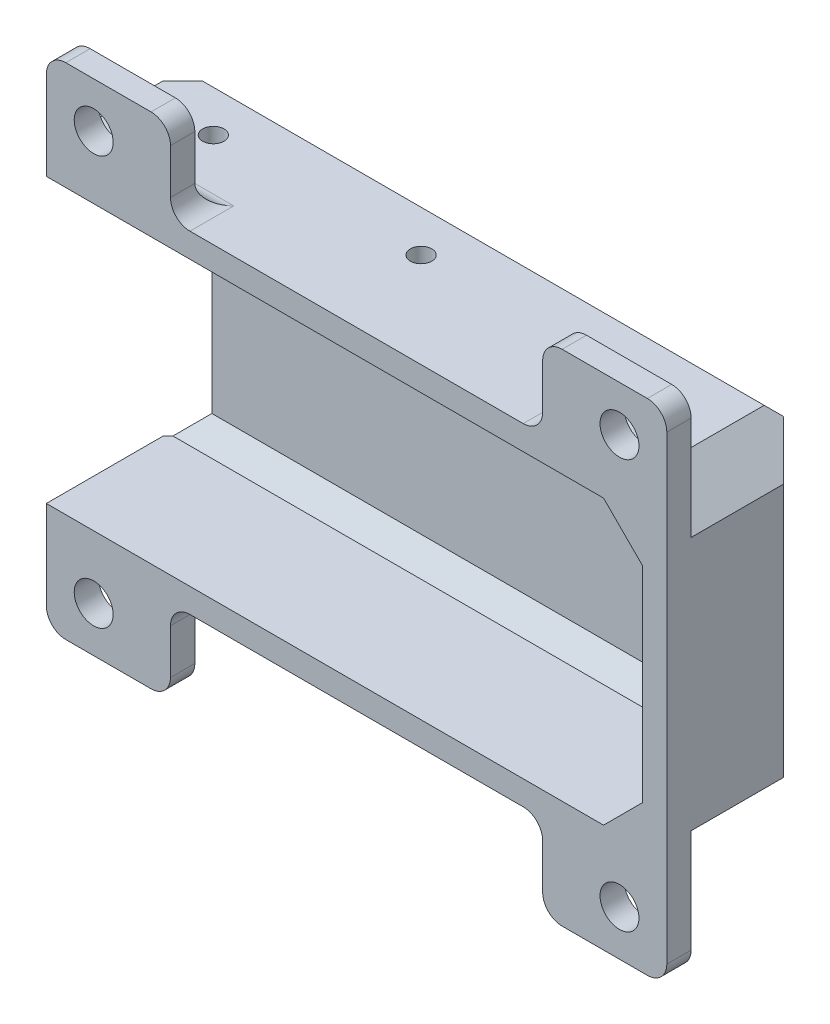
SolidWorks part; units mm, degrees
ref_plane "前视基准面" through (0, 0, 0) normal (0, 0, 1) x (1, 0, 0)
ref_plane "上视基准面" through (0, 0, 0) normal (0, 1, 0) x (1, 0, 0)
ref_plane "右视基准面" through (0, 0, 0) normal (1, 0, 0) x (0, 0, -1)
sketch "草图1" plane through (0, 0, 0) normal (0, 0, 1) x (1, 0, 0)
  line L1 (47.2241, 30.3103) -> (-6.7759, 30.3103) construction
  line L2 (47.2241, 30.3103) -> (47.2241, -11.6897) construction
  line L3 (47.2241, -11.6897) -> (-6.7759, -11.6897) construction
  line L4 (-6.7759, 30.3103) -> (-6.7759, -11.6897) construction
  line L5 (47.2241, 30.3103) -> (-6.7759, -11.6897) construction
  line L6 (47.2241, -11.6897) -> (-6.7759, 30.3103) construction
  line L7 (-11.6379, 34.9655) -> (52.0862, 34.9655)
  line L8 (-11.6379, 34.9655) -> (-11.6379, -16.3448)
  line L9 (-11.6379, -16.3448) -> (52.0862, -16.3448)
  line L10 (52.0862, 34.9655) -> (52.0862, -16.3448)
  line L11 (-11.6379, 34.9655) -> (52.0862, -16.3448) construction
  line L12 (-11.6379, -16.3448) -> (52.0862, 34.9655) construction
  circle A0 centre (47.2241, 30.3103) radius 2
  circle A1 centre (-6.7759, 30.3103) radius 2
  circle A2 centre (-6.7759, -11.6897) radius 2
  circle A3 centre (47.2241, -11.6897) radius 2
  point P0 (20.2241, 9.3103)
  point P9 (20.2241, 9.3103)
  dimension "D1" = 42
  dimension "D2" = 54
extrude "凸台-拉伸1" add sketch "草图1" along normal blind 2.5
sketch "草图2" plane through (0, 0, 0) normal (0, 0, -1) x (-1, 0, 0)
  line L0 (-52.0862, 9.3103) -> (-48.5569, 9.3103) construction
  line L2 (-20.2241, 34.9655) -> (-20.2241, 32.4809) construction
  line L4 (11.6379, 34.9655) -> (11.6379, -16.3448) construction
  line L5 (-52.0862, 26.3557) -> (11.6379, 26.3557)
  line L6 (-52.0862, 26.3557) -> (-52.0862, -7.735)
  line L7 (-52.0862, -7.735) -> (11.6379, -7.735)
  line L8 (11.6379, 26.3557) -> (11.6379, -7.735)
  line L9 (-52.0862, 26.3557) -> (11.6379, -7.735) construction
  line L10 (-52.0862, -7.735) -> (11.6379, 26.3557) construction
  point P2 (-20.2241, 9.3103)
extrude "凸台-拉伸2" add sketch "草图2" along normal blind 13.5
sketch "草图3" plane through (52.0862, 0, 0) normal (1, 0, 0) x (0, 0, -1)
  line L0 (-2.5, 9.3103) -> (2.413, 9.3103) construction
  line L2 (-2.5, -16.3448) -> (-2.5, 34.9655) construction
  line L3 (-17, 23.8557) -> (12, 23.8557)
  line L4 (-17, 23.8557) -> (-17, -5.235)
  line L5 (-17, -5.235) -> (12, -5.235)
  line L6 (12, 23.8557) -> (12, -5.235)
  line L7 (-17, 23.8557) -> (12, -5.235) construction
  line L8 (-17, -5.235) -> (12, 23.8557) construction
  line L9 (13.5, 26.3557) -> (13.5, -7.735) construction
  line L10 (13.5, 26.3557) -> (0, 26.3557) construction
  point P1 (-2.5, 9.3103)
  dimension "D1" = 1.5
  dimension "D2" = 2.5
extrude "切除-拉伸1" cut sketch "草图3" against normal through all both and the other way through all
chamfer "倒角1" distance 2 angle 45 4 edges at (20.2241, 26.3557, -13.5) (20.2241, -7.735, -13.5) (20.2241, -5.235, -12) (20.2241, 23.8557, -12)
sketch "草图4" plane through (0, 0, 0) normal (0, 0, -1) x (-1, 0, 0)
  line L0 (-20.2241, 34.9655) -> (-20.2241, 29.0132) construction
  line L2 (-52.0862, 34.9655) -> (11.6379, 34.9655) construction
  line L3 (-39.3359, 43.5754) -> (-1.1123, 43.5754)
  line L4 (-39.3359, 43.5754) -> (-39.3359, 26.3557)
  line L5 (-39.3359, 26.3557) -> (-1.1123, 26.3557)
  line L6 (-1.1123, 43.5754) -> (-1.1123, 26.3557)
  line L7 (-39.3359, 43.5754) -> (-1.1123, 26.3557) construction
  line L8 (-39.3359, 26.3557) -> (-1.1123, 43.5754) construction
  line L9 (11.6379, 26.3557) -> (-52.0862, 26.3557) construction
  line L10 (-52.0862, -7.735) -> (11.6379, -7.735) construction
  line L11 (-39.3359, -24.401) -> (-1.1123, -24.401)
  line L12 (-39.3359, -24.401) -> (-39.3359, -7.735)
  line L13 (-39.3359, -7.735) -> (-1.1123, -7.735)
  line L14 (-1.1123, -24.401) -> (-1.1123, -7.735)
  line L15 (-39.3359, -24.401) -> (-1.1123, -7.735) construction
  line L16 (-39.3359, -7.735) -> (-1.1123, -24.401) construction
  point P1 (-20.2241, 34.9655)
  point P11 (-20.2241, -16.068)
extrude "切除-拉伸2" cut sketch "草图4" against normal through all both and the other way through all
fillet "圆角1" radius 2 12 edges at (39.3359, -7.735, 1.25) (1.1123, -7.735, 1.25) (1.1123, 26.3557, 1.25) (1.1123, 34.9655, 1.25) (-11.6379, 34.9655, 1.25) (-11.6379, -16.3448, 1.25) (1.1123, -16.3448, 1.25) (39.3359, -16.3448, 1.25) (52.0862, -16.3448, 1.25) (39.3359, 26.3557, 1.25) (39.3359, 34.9655, 1.25) (52.0862, 34.9655, 1.25)
sketch "草图5" plane through (0, 0, -12) normal (0, 0, 1) x (1, 0, 0)
  line L0 (52.0862, 9.3103) -> (49.5933, 9.3103) construction
  line L2 (-11.6379, 23.8557) -> (52.0862, 23.8557) construction
  line L3 (49.5862, 23.8557) -> (52.0862, 23.8557)
  line L4 (49.5862, 23.8557) -> (49.5862, -5.235)
  line L5 (49.5862, -5.235) -> (52.0862, -5.235)
  line L6 (52.0862, 23.8557) -> (52.0862, -5.235)
  dimension "D1" = 2.5
extrude "凸台-拉伸3" add sketch "草图5" along normal up to surface (14.5 mm away) up to face at (20.2241, -12.0712, 2.5)
chamfer "倒角2" distance 1 angle 45 1 edges at (49.5862, 9.3103, -12)
chamfer "倒角3" distance 4 angle 45 6 edges at (52.0862, 26.3557, -5.75) (52.0862, -7.735, -5.75) (49.5862, -5.235, -3.75) (49.5862, 23.8557, -3.75) (52.0862, 9.3103, -13.5) (-11.6379, 9.3103, -13.5)
sketch "草图6" plane through (0, 26.3557, 0) normal (0, 1, 0) x (1, 0, 0)
  line L0 (-11.6379, 7.25) -> (-9.702, 7.25) construction
  circle A0 centre (-4.2353, 7.25) radius 1.1
  circle A1 centre (17.1021, 7.25) radius 1.1
  circle A2 centre (39.6196, 7.25) radius 1.1
extrude "切除-拉伸3" cut sketch "草图6" against normal blind 15.5
fillet "圆角2" radius 2 4 edges at (42.7111, 26.3557, 0) (-4.2628, 26.3557, 0) (42.7111, -7.735, 0) (-4.2628, -7.735, 0)
